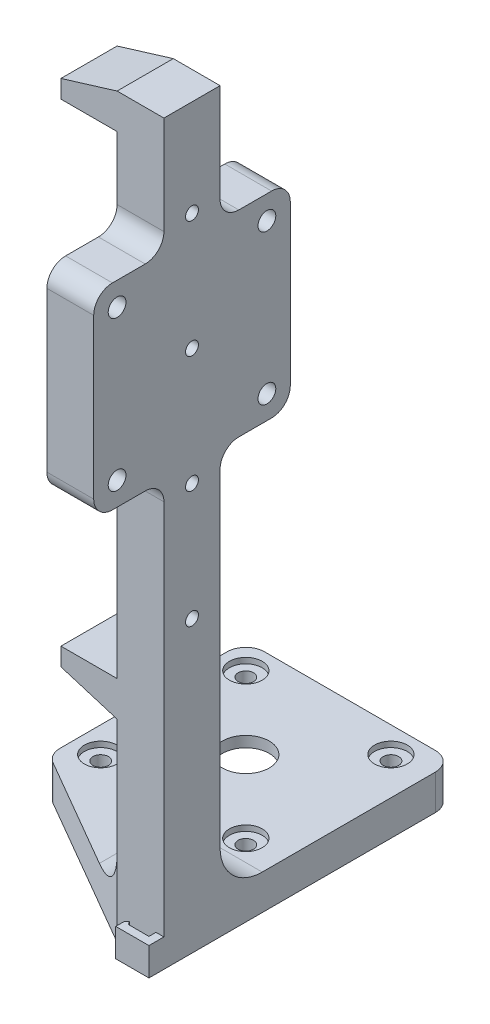
SolidWorks part; units mm, degrees
ref_plane "Front Plane" through (0, 0, 0) normal (0, 0, 1) x (1, 0, 0)
ref_plane "Top Plane" through (0, 0, 0) normal (0, 1, 0) x (1, 0, 0)
ref_plane "Right Plane" through (0, 0, 0) normal (1, 0, 0) x (0, 0, -1)
sketch "Sketch1" plane through (0, 0, 0) normal (1, 0, 0) x (0, 0, -1)
  line L1 (-21, 21) -> (21, 21)
  line L2 (-21, 21) -> (-21, -21)
  line L3 (-21, -21) -> (21, -21)
  line L4 (21, 21) -> (21, -21)
  line L5 (-21, 21) -> (21, -21) construction
  line L6 (-21, -21) -> (21, 21) construction
  circle A0 centre (16, -16) radius 1.9
  circle A1 centre (-16, -16) radius 1.9
  circle A2 centre (-16, 16) radius 1.9
  circle A3 centre (16, 16) radius 1.9
  point P0 (0, 0)
  dimension "D1" = 3.8
  dimension "D2" = 16
  dimension "D5" = 16
  dimension "D6" = 42
  dimension "D3" = 2
  dimension "D4" = 2
extrude "Boss-Extrude1" add sketch "Sketch1" along normal blind 10
sketch "Sketch2" plane through (0, 0, 0) normal (-1, 0, 0) x (0, 0, 1)
  line L0 (21, 21) -> (21, -21) construction
  line L1 (6, 46) -> (-6, 46)
  line L2 (6, 46) -> (6, -104)
  line L3 (6, -104) -> (-6, -104)
  line L4 (-6, 46) -> (-6, -104)
  line L5 (6, 46) -> (-6, -104) construction
  line L6 (6, -104) -> (-6, 46) construction
  line L7 (0, 46) -> (0, -104) construction
  line L8 (-21, 21) -> (21, 21) construction
  point P0 (0, -29)
  dimension "D1" = 12
  dimension "D2" = 21
  dimension "D3" = 150
  dimension "D4" = 25
extrude "Boss-Extrude2" add sketch "Sketch2" against normal blind 10
sketch "Sketch3" plane through (0, 0, 0) normal (-1, 0, 0) x (0, 0, 1)
  line L0 (-6, 38.5) -> (6, 38.5) construction
  line L1 (-6, 46) -> (-6, 21) construction
  line L2 (6, 21) -> (6, 46) construction
  line L3 (6, 46) -> (-6, 46) construction
  line L4 (6, -104) -> (6, -21) construction
  line L5 (6, 38.5) -> (-6, 38.5)
  line L6 (6, 38.5) -> (6, 42.25)
  line L7 (6, 42.25) -> (-6, 42.25)
  line L8 (-6, 38.5) -> (-6, 42.25)
  line L9 (-6, -66.45) -> (6, -66.45)
  line L10 (-6, -66.45) -> (-6, -62.7)
  line L11 (-6, -62.7) -> (6, -62.7)
  line L12 (6, -66.45) -> (6, -62.7)
  dimension "D1" = 7.5
  dimension "D2" = 3.75
  dimension "D3" = 101.2
  dimension "D4" = 3.75
extrude "Boss-Extrude3" add sketch "Sketch3" along normal blind 12
chamfer "Chamfer1" distance 3.75 angle 73 2 edges at (0, 42.25, 0) (0, -66.45, 0) first distance on face at (0, 44.125, 0) first distance on face at (0, -85.225, 0)
sketch "Sketch4" plane through (0, 0, 0) normal (-1, 0, 0) x (0, 0, 1)
  line L0 (0, 38.5) -> (0, -104) construction
  line L1 (-6, 38.5) -> (6, 38.5) construction
  line L2 (-6, -104) -> (6, -104) construction
  circle A0 centre (0, 25.4) radius 1.375
  circle A1 centre (0, 0.4) radius 1.375
  circle A2 centre (0, -24.6) radius 1.375
  circle A3 centre (0, -49.6) radius 1.375
  dimension "D1" = 2.75
  dimension "D2" = 13.1
  dimension "D3" = 4
extrude "Cut-Extrude1" cut sketch "Sketch4" against normal blind 12
sketch "Sketch5" plane through (0, -104, 0) normal (0, -1, 0) x (1, 0, 0)
  line L0 (10, -6) -> (10, 6) construction
  line L1 (10, 6) -> (10, -56)
  line L2 (-34.5, -14) -> (7.5, -14)
  line L3 (-34.5, -14) -> (-34.5, -56)
  line L4 (-34.5, -56) -> (7.5, -56)
  line L5 (7.5, -14) -> (7.5, -56)
  line L6 (-34.5, -14) -> (7.5, -56) construction
  line L7 (-34.5, -56) -> (7.5, -14) construction
  line L8 (10, -56) -> (7.5, -56)
  line L9 (0, 6) -> (-34.5, -14)
  line L10 (0, 6) -> (10, 6)
  circle A0 centre (-13.5, -35) radius 5
  circle A1 centre (2, -50.5) radius 1.65
  circle A2 centre (-29, -50.5) radius 1.65
  circle A3 centre (-29, -19.5) radius 1.65
  circle A4 centre (2, -19.5) radius 1.65
  line M5 (10, 6) -> (0, 6)
  line M7 (0, -6) -> (10, -6)
  line M8 (10, -6) -> (10, 6)
  dimension "D5" = 3.3
  dimension "D9" = 10
  dimension "D1" = 35
  dimension "D2" = 23.5
  dimension "D3" = 42
  dimension "D4" = 42
  dimension "D6" = 15.5
  dimension "D7" = 2
  dimension "D8" = 2
extrude "Boss-Extrude4" add sketch "Sketch5" along normal blind 7.5 contours L5 L2 L3 L4 A4 A3 A2 A1 A0 | L2 L5 L8 L1 M7 | M8 M5 M7 region at (-3.1519, -104, -10.7769) region at (-13.5, -104, -14.594)
sketch "Sketch6" plane through (0, -111.5, 0) normal (0, -1, 0) x (1, 0, 0)
  circle A0 centre (-13.5, -35) radius 12.5
  dimension "D1" = 25
extrude "Cut-Extrude2" cut sketch "Sketch6" against normal blind 5.2
sketch "Sketch7" [suppressed] plane through (10, 0, 0) normal (1, 0, 0) x (0, 0, -1)
  line L0 (-6, 39) -> (6, 39) construction
  line L1 (-1.7321, 15.65) -> (1.7321, 15.65)
  line L2 (1.7321, 15.65) -> (3.4641, 18.65)
  line L3 (3.4641, 18.65) -> (1.7321, 21.65)
  line L4 (1.7321, 21.65) -> (-1.7321, 21.65)
  line L5 (-1.7321, 21.65) -> (-3.4641, 18.65)
  line L6 (-3.4641, 18.65) -> (-1.7321, 15.65)
  line L7 (-1.7321, -9.35) -> (1.7321, -9.35)
  line L8 (1.7321, -9.35) -> (3.4641, -6.35)
  line L9 (3.4641, -6.35) -> (1.7321, -3.35)
  line L10 (1.7321, -3.35) -> (-1.7321, -3.35)
  line L11 (-1.7321, -3.35) -> (-3.4641, -6.35)
  line L12 (-3.4641, -6.35) -> (-1.7321, -9.35)
  line L13 (-1.7321, -34.35) -> (1.7321, -34.35)
  line L14 (1.7321, -34.35) -> (3.4641, -31.35)
  line L15 (3.4641, -31.35) -> (1.7321, -28.35)
  line L16 (1.7321, -28.35) -> (-1.7321, -28.35)
  line L17 (-1.7321, -28.35) -> (-3.4641, -31.35)
  line L18 (-3.4641, -31.35) -> (-1.7321, -34.35)
  line L19 (-1.7321, -59.35) -> (1.7321, -59.35)
  line L20 (1.7321, -59.35) -> (3.4641, -56.35)
  line L21 (3.4641, -56.35) -> (1.7321, -53.35)
  line L22 (1.7321, -53.35) -> (-1.7321, -53.35)
  line L23 (-1.7321, -53.35) -> (-3.4641, -56.35)
  line L24 (-3.4641, -56.35) -> (-1.7321, -59.35)
  circle A0 centre (0, 18.65) radius 3 construction
  dimension "D1" = 6
  dimension "D2" = 4
extrude "Cut-Extrude3" [suppressed] cut sketch "Sketch7" against normal blind 5
fillet "Fillet1" radius 4 11 edges at (10, -107.75, -56) (-34.5, -107.75, -56) (-34.5, -107.75, -14) (5, 21, 6) (5, 21, -6) (5, -21, -6) (5, -21, 6) (5, -21, 21) (5, -21, -21) (5, 21, 21) (5, 21, -21)
fillet "Fillet2" radius 9 2 edges at (5, -104, -6) (0, -104, 0)
sketch "Sketch8" plane through (0, -104, 0) normal (0, 1, 0) x (1, 0, 0)
  circle A0 centre (-29, 50.5) radius 3.5
  circle A2 centre (2, 50.5) radius 3.5
  circle A3 centre (2, 19.5) radius 3.5
  circle A4 centre (-29, 19.5) radius 3.5
  dimension "D1" = 7
  dimension "D2" = 2
  dimension "D3" = 2
extrude "Cut-Extrude4" cut sketch "Sketch8" against normal blind 1.2
sketch "Sketch11" plane through (0, -111.5, 0) normal (0, -1, 0) x (1, 0, 0)
  line L0 (10, 6) -> (10, 9.2)
  line L1 (10, 9.2) -> (2.9, 9.2)
  line L2 (2.9, 9.2) -> (2.9, 7.5)
  line L3 (2.9, 7.5) -> (8.3, 7.5)
  line L4 (8.3, 7.5) -> (8.3, 6)
  line L5 (2.9, 7.5) -> (3.4334, 6.8)
  line L6 (3.4334, 6.8) -> (3.9, 7.5)
  line L7 (3.9, 7.5) -> (2.9, 7.5)
  line L8 (8.3, 6) -> (10, 6)
  line M9 (10, 6) -> (0, 6)
  dimension "D1" = 1.7
  dimension "D2" = 1.7
  dimension "D3" = 5.4
  dimension "D4" = 4.4
  dimension "D5" = 0.7
extrude "Boss-Extrude7" add sketch "Sketch11" against normal blind 6 contours L3 L4 L0 L1 L2 M9 | L5 L6 L3 region at (6.9209, -111.5, 8.0709) region at (3.4111, -111.5, 7.2667)
